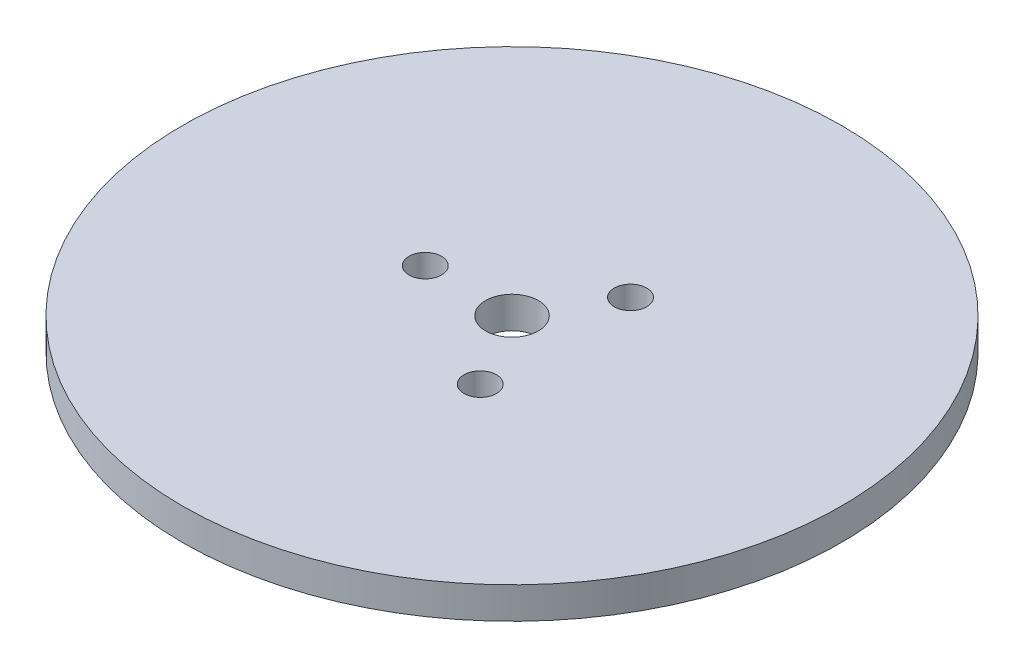
SolidWorks part; units mm, degrees
ref_plane "Front Plane" through (0, 0, 0) normal (0, 0, 1) x (1, 0, 0)
ref_plane "Top Plane" through (0, 0, 0) normal (0, 1, 0) x (1, 0, 0)
ref_plane "Right Plane" through (0, 0, 0) normal (1, 0, 0) x (0, 0, -1)
sketch "Sketch1" plane through (0, 0, 0) normal (0, 1, 0) x (1, 0, 0)
  circle A0 centre (0, 0) radius 62.5
  dimension "FLANGE_OD" = 125
extrude "Boss-Extrude1" add sketch "Sketch1" along normal blind 6
sketch "Sketch2" plane through (0, 0, 0) normal (0, 1, 0) x (1, 0, 0)
  circle A0 centre (0, 0) radius 5
  dimension "BORE_D" = 10
extrude "Cut-Extrude1" cut sketch "Sketch2" along normal through all
sketch "Sketch3" plane through (0, 6, 0) normal (0, 1, 0) x (1, 0, 0)
  circle A0 centre (0, 0) radius 16.4489 construction
  circle A1 centre (-16.4489, 0) radius 3.0824
  dimension "BOLT_D" = 6.1647
  dimension "BOLT_PCD" = 32.8978
extrude "Cut-Extrude2" cut sketch "Sketch3" against normal blind 4.4123
pattern_circular "CirPattern1" count 3 over 360 about axis through (0, 0, 0) along (0, 1, 0) of "Cut-Extrude2"
